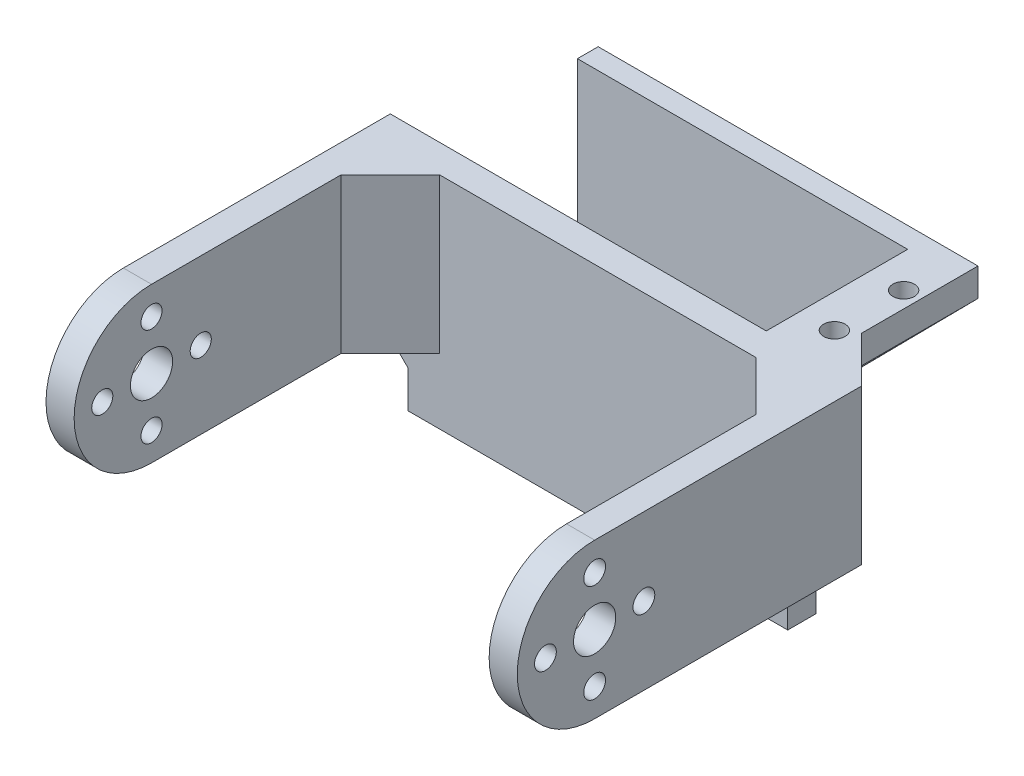
SolidWorks part; units mm, degrees
ref_plane "Front Plane" through (0, 0, 0) normal (0, 0, 1) x (1, 0, 0)
ref_plane "Top Plane" through (0, 0, 0) normal (0, 1, 0) x (1, 0, 0)
ref_plane "Right Plane" through (0, 0, 0) normal (1, 0, 0) x (0, 0, -1)
sketch "Sketch1" plane through (0, 0, 0) normal (0, 1, 0) x (1, 0, 0)
  line L0 (0, 0) -> (0, 50)
  line L1 (0, 50) -> (67, 50)
  line L2 (67, 50) -> (67, 0)
  line L3 (67, 0) -> (63, 0)
  line L4 (63, 0) -> (63, 46)
  line L5 (63, 46) -> (4, 46)
  line L6 (4, 46) -> (4, 0)
  line L7 (4, 0) -> (0, 0)
  dimension "67" = 67
  dimension "D2" = 4
  dimension "D3" = 4
  dimension "4" = 4
  dimension "D4" = 50
extrude "Boss-Extrude1" add sketch "Sketch1" along normal blind 22
sketch "Sketch3" plane through (67, 0, 0) normal (1, 0, 0) x (0, 0, -1)
  line L0 (0, 11) -> (12.05, 11) construction
  line L1 (0, 22) -> (0, 0) construction
  circle A0 centre (12.05, 11) radius 1.55
  dimension "D1" = 3.1
extrude "Cut-Extrude1" cut sketch "Sketch3" against normal blind 30
sketch "Sketch5" plane through (67, 0, 0) normal (1, 0, 0) x (0, 0, -1)
  line L0 (12.05, 22) -> (0, 22)
  line L1 (0, 22) -> (0, 0)
  line L2 (0, 0) -> (12.05, 0)
  arc A0 (12.05, 22) -> (12.05, 0) centre (12.05, 11) ccw
extrude "Cut-Extrude5" cut sketch "Sketch5" against normal blind 9
sketch "Sketch11" plane through (67, 0, 0) normal (1, 0, 0) x (0, 0, -1)
  line L0 (12.05, 11) -> (12.05, 22) construction
  line L1 (12.05, 22) -> (12.05, 0) construction
  line L2 (50, 11) -> (1.05, 11) construction
  line L3 (50, 22) -> (50, 0) construction
  line L4 (12.05, 22) -> (50, 22) construction
  line L5 (50, 20.5119) -> (1.05, 20.5119) construction
  line L6 (50, 1.7853) -> (1.05, 1.7853) construction
  line L7 (1.05, 1.7853) -> (1.05, 20.5119) construction
  line L8 (3.1114, 20.5119) -> (3.1114, 1.7853) construction
  line L9 (19.05, 20.5119) -> (19.05, 1.7853) construction
  arc A0 (12.05, 22) -> (12.05, 0) centre (12.05, 11) ccw construction
  circle A1 centre (19.05, 11) radius 1.55
  circle A2 centre (12.05, 18) radius 1.55
  circle A3 centre (12.05, 4) radius 1.55
  circle A4 centre (5.05, 11) radius 1.55
  dimension "D3" = 3.1
  dimension "D4" = 30.95
  dimension "1.5" = 3.1
  dimension "3.1" = 3.1
  dimension "D7" = 3.1
  dimension "D8" = 7
  dimension "D9" = 7
  dimension "D1" = 11
  dimension "D2" = 30.95
  dimension "D5" = 7
  dimension "7" = 7
extrude "Cut-Extrude10" cut sketch "Sketch11" against normal blind 13
sketch "Sketch12" plane through (0, 0, 0) normal (-1, 0, 0) x (0, 0, 1)
  line L0 (-12.05, 22) -> (0, 22)
  line L1 (0, 22) -> (0, 0)
  line L2 (0, 0) -> (-12.05, 0)
  arc A0 (-12.05, 0) -> (-12.05, 22) centre (-12.05, 11) ccw
extrude "Cut-Extrude11" cut sketch "Sketch12" against normal blind 10
sketch "Sketch13" plane through (0, 0, 0) normal (-1, 0, 0) x (0, 0, 1)
  line L0 (-12.05, 14) -> (-12.05, 22) construction
  line L1 (-12.05, 22) -> (-9.05, 11) construction
  line L2 (-9.05, 11) -> (-1.05, 11) construction
  line L3 (-1.05, 11) -> (-12.05, 8) construction
  line L4 (-12.05, 8) -> (-12.05, 0) construction
  line L5 (-12.05, 0) -> (-15.05, 11) construction
  line L6 (-15.05, 11) -> (-23.05, 11) construction
  line L7 (-23.05, 11) -> (-12.05, 14) construction
  circle A0 centre (-12.05, 11) radius 3
  arc A1 (-12.05, 0) -> (-12.05, 22) centre (-12.05, 11) ccw construction
  circle A2 centre (-19.05, 11) radius 1.5
  circle A3 centre (-12.05, 4) radius 1.5
  circle A4 centre (-5.05, 11) radius 1.5
  circle A5 centre (-12.05, 18) radius 1.5
  dimension "D1" = 6
  dimension "D2" = 3
  dimension "D3" = 3
  dimension "3" = 3
  dimension "D4" = 3
  dimension "8" = 8
extrude "Cut-Extrude12" cut sketch "Sketch13" against normal blind 72
fillet "Fillet1" radius 7 2 edges at (63, 11, -46) (4, 11, -46) profile chamfer
sketch "Sketch14" plane through (0, 0, -50) normal (0, 0, -1) x (-1, 0, 0)
  line L0 (-60.5, 22) -> (-6.5, 22)
  line L1 (-67, 22) -> (0, 22) construction
  line L2 (-67, 22) -> (-67, 0) construction
  line L3 (0, 22) -> (0, 0) construction
  line L5 (-6.5, 22) -> (-13.55, 22)
  line L6 (-6.5, 22) -> (-6.5, 18)
  line L7 (-6.5, 18) -> (-13.55, 18)
  line L8 (-13.55, 22) -> (-13.55, 18)
  line L9 (-60.5, 22) -> (-53.45, 22)
  line L10 (-60.5, 22) -> (-60.5, 18)
  line L11 (-60.5, 18) -> (-53.45, 18)
  line L12 (-53.45, 22) -> (-53.45, 18)
  line L17 (-67, 0) -> (0, 0) construction
  line L18 (-60.5, 0) -> (-6.5, 0)
  line L19 (-60.5, 0) -> (-60.5, -9.3)
  line L20 (-60.5, -9.3) -> (-6.5, -9.3)
  line L21 (-6.5, 0) -> (-6.5, -9.3)
  line M6 (-67, 0) -> (0, 0)
  line M8 (0, 22) -> (-67, 22)
  dimension "D1" = 6.5
  dimension "D2" = 6.5
  dimension "D3" = 7.05
  dimension "D4" = 7.05
  dimension "D5" = 4
  dimension "D6" = 4
  dimension "D7" = 9.3
extrude "Boss-Extrude4" add sketch "Sketch14" against normal blind 4 contours L21 L19 L20 M6 | L12 L10 L11 M8 | L8 L7 L6 M8 region at (10.025, 20, -50) region at (56.975, 20, -50) region at (33.5, -4.65, -50)
sketch "Sketch17" plane through (0, 0, -50) normal (0, 0, -1) x (-1, 0, 0)
  line L0 (-67, 22) -> (0, 22) construction
  line L1 (-60.5, 22) -> (-53.45, 22)
  line L2 (-60.5, 22) -> (-60.5, 18)
  line L3 (-60.5, 18) -> (-53.45, 18)
  line L4 (-53.45, 22) -> (-53.45, 18)
  line L5 (-67, 22) -> (-67, 0) construction
  line L6 (-13.55, 22) -> (-6.5, 22)
  line L7 (-13.55, 22) -> (-13.55, 18)
  line L8 (-13.55, 18) -> (-6.5, 18)
  line L9 (-6.5, 22) -> (-6.5, 18)
  line L10 (0, 22) -> (0, 0) construction
  dimension "D1" = 6.5
  dimension "D2" = 4
  dimension "D3" = 7.05
  dimension "D4" = 6.5
  dimension "D5" = 4
  dimension "D6" = 7.05
extrude "Boss-Extrude5" add sketch "Sketch17" along normal blind 23.05
sketch "Sketch18" plane through (0, 18, 0) normal (0, -1, 0) x (1, 0, 0)
  line L0 (6.5, -73.05) -> (6.5, -50) construction
  line L1 (60.5, -73.05) -> (6.5, -73.05)
  line L2 (60.5, -73.05) -> (60.5, -70.1)
  line L3 (60.5, -70.1) -> (6.5, -70.1)
  line L4 (6.5, -73.05) -> (6.5, -70.1)
  dimension "D1" = 2.95
extrude "Boss-Extrude6" add sketch "Sketch18" along normal up to vertex (27.3 mm away) and the other way blind 4 up to point (60.5, -9.3, -50)
sketch "Sketch19" plane through (0, 0, -50) normal (0, 0, -1) x (-1, 0, 0)
  line L0 (-60.5, 22) -> (-60.5, -9.3) construction
  line L1 (-6.5, 22) -> (-60.5, 22) construction
  line L2 (-6.5, -9.3) -> (-60.5, -9.3)
  line L3 (-6.5, -9.3) -> (-6.5, -6.5)
  line L4 (-6.5, -6.5) -> (-60.5, -6.5)
  line L5 (-60.5, -9.3) -> (-60.5, -6.5)
  dimension "D1" = 28.5
extrude "Boss-Extrude7" add sketch "Sketch19" along normal blind 21
fillet "Fillet2" radius 6.5 2 edges at (60.5, 20, -50) (6.5, 20, -50) profile chamfer
sketch "Sketch20" plane through (0, -9.3, 0) normal (0, -1, 0) x (1, 0, 0)
  line L0 (23.4, -73.05) -> (23.4, -46) construction
  line L1 (6.5, -73.05) -> (60.5, -73.05) construction
  line L2 (60.5, -46) -> (6.5, -46) construction
  line L3 (6.5, -46) -> (6.5, -73.05) construction
  circle A0 centre (23.4, -59.65) radius 2.625
  dimension "D1" = 5.25
  dimension "13.5" = 13.4
  dimension "D2" = 16.9
extrude "Boss-Extrude8" add sketch "Sketch20" along normal blind 6
fillet "Fillet4" radius 1 1 edges at (23.4, -15.3, -62.275)
sketch "Sketch22" plane through (0, 0, -73.05) normal (0, 0, -1) x (-1, 0, 0)
  line L0 (-60.5, -9.3) -> (-33.5, -9.3)
  line L1 (-6.5, -9.3) -> (-60.5, -9.3) construction
  line L2 (-33.5, -9.3) -> (-60.5, 18)
  line L3 (-60.5, 22) -> (-60.5, -9.3) construction
  line L4 (-60.5, 18) -> (-60.5, -9.3)
  line L5 (-6.5, 22) -> (-60.5, 22) construction
  dimension "D1" = 4
  dimension "D2" = 27
extrude "Cut-Extrude15" cut sketch "Sketch22" against normal blind 23.05
sketch "Sketch23" plane through (0, 22, 0) normal (0, 1, 0) x (1, 0, 0)
  line L1 (13.55, 70.1) -> (-4.8108, 70.1)
  line L2 (13.55, 70.1) -> (13.55, 50)
  line L3 (13.55, 50) -> (-4.8108, 50)
  line L4 (-4.8108, 70.1) -> (-4.8108, 50)
extrude "Cut-Extrude16" cut sketch "Sketch23" against normal blind 23
fillet "Fillet7" radius 4 1 edges at (6.5, 0, -48) profile chamfer
sketch "Sketch26" plane through (0, 22, 0) normal (0, 1, 0) x (1, 0, 0)
  line L0 (58.21, 73.05) -> (58.21, 46.2591) construction
  line L1 (6.5, 73.05) -> (60.5, 73.05) construction
  line L2 (60.5, 73.05) -> (60.5, 56.5) construction
  circle A0 centre (58.21, 64.77) radius 1.525
  circle A1 centre (58.21, 54.92) radius 1.525
  dimension "D2" = 8.28
  dimension "D3" = 3.05
  dimension "D4" = 9.85
  dimension "D5" = 3.05
  dimension "D1" = 2.29
extrude "Cut-Extrude18" cut sketch "Sketch26" against normal blind 11.5
